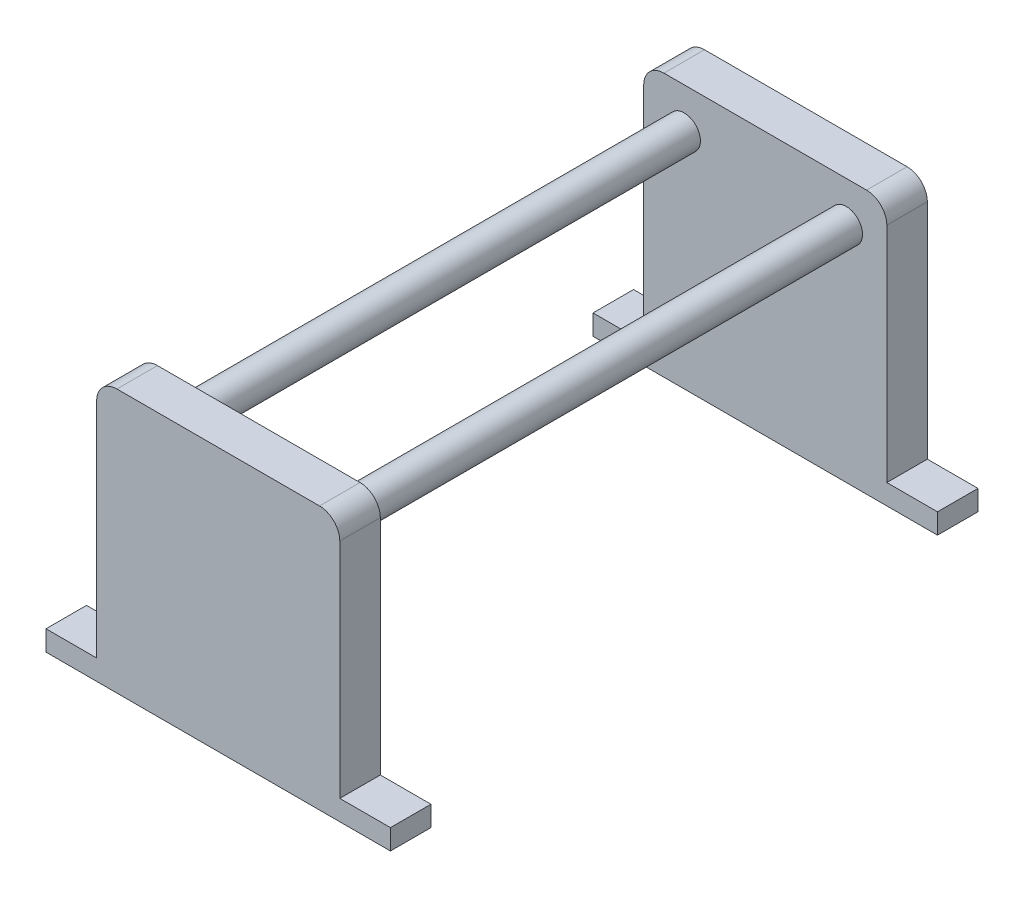
SolidWorks part; units mm, degrees
ref_plane "Alzado" through (0, 0, 0) normal (0, 0, 1) x (1, 0, 0)
ref_plane "Planta" through (0, 0, 0) normal (0, 1, 0) x (1, 0, 0)
ref_plane "Vista lateral" through (0, 0, 0) normal (1, 0, 0) x (0, 0, -1)
sketch "Croquis1" plane through (0, 0, 0) normal (0, 0, 1) x (1, 0, 0)
  line L1 (30, 30) -> (-30, 30)
  line L2 (30, 30) -> (30, -30)
  line L3 (30, -30) -> (-30, -30)
  line L4 (-30, 30) -> (-30, -30)
  line L5 (30, 30) -> (-30, -30) construction
  line L6 (30, -30) -> (-30, 30) construction
  line L7 (-42.5, -30) -> (42.5, -30)
  line L8 (-42.5, -30) -> (-42.5, -35)
  line L9 (-42.5, -35) -> (42.5, -35)
  line L10 (42.5, -30) -> (42.5, -35)
  line L11 (-42.5, -30) -> (42.5, -35) construction
  line L12 (-42.5, -35) -> (42.5, -30) construction
  point P0 (0, 0)
  point P10 (0, -32.5)
  point P11 (0, 0)
  dimension "D1" = 60
  dimension "D2" = 5
  dimension "D3" = 85
extrude "Saliente-Extruir1" add sketch "Croquis1" along normal blind 10 contours L1 L4 L3 L2 | L10 L7 L3 L8 L9 region at (0, 0, 0) region at (0, -32.5, 0)
fillet "Redondeo1" radius 5 2 edges at (30, 30, 5) (-30, 30, 5)
sketch "Croquis2" plane through (0, 0, 0) normal (0, 0, -1) x (-1, 0, 0)
  line L0 (0, 30) -> (0, -35) construction
  line L1 (-25, 30) -> (25, 30) construction
  line L2 (42.5, -35) -> (-42.5, -35) construction
  line L3 (-30, 25) -> (-30, -30) construction
  circle A0 centre (-20, 20) radius 4
  circle A1 centre (20, 20) radius 4
  dimension "D1" = 10
  dimension "D3" = 8
  dimension "D2" = 10
extrude "Saliente-Extruir2" add sketch "Croquis2" along normal blind 125
sketch "Croquis3" plane through (0, 0, -125) normal (0, 0, -1) x (-1, 0, 0)
  line L1 (-30, 30) -> (30, 30)
  line L2 (-30, 30) -> (-30, -30)
  line L3 (-30, -30) -> (30, -30)
  line L4 (30, 30) -> (30, -30)
  line L5 (-30, 30) -> (30, -30) construction
  line L6 (-30, -30) -> (30, 30) construction
  line L7 (42.5, -30) -> (-42.5, -30)
  line L8 (42.5, -30) -> (42.5, -35)
  line L9 (42.5, -35) -> (-42.5, -35)
  line L10 (-42.5, -30) -> (-42.5, -35)
  line L11 (42.5, -30) -> (-42.5, -35) construction
  line L12 (42.5, -35) -> (-42.5, -30) construction
  point P4 (0, 0)
  point P10 (0, -32.5)
  circle M2 centre (20, 20) radius 4
  dimension "D1" = 60
extrude "Saliente-Extruir4" add sketch "Croquis3" along normal blind 10 contours L4 L1 L2 L3 M2 | L7 L10 L9 L8 L3 | M2 region at (0.2832, -0.2832, -125) region at (0, -32.5, -125) region at (-20, 20, -125)
fillet "Redondeo2" radius 5 2 edges at (30, 30, -130) (-30, 30, -130)
